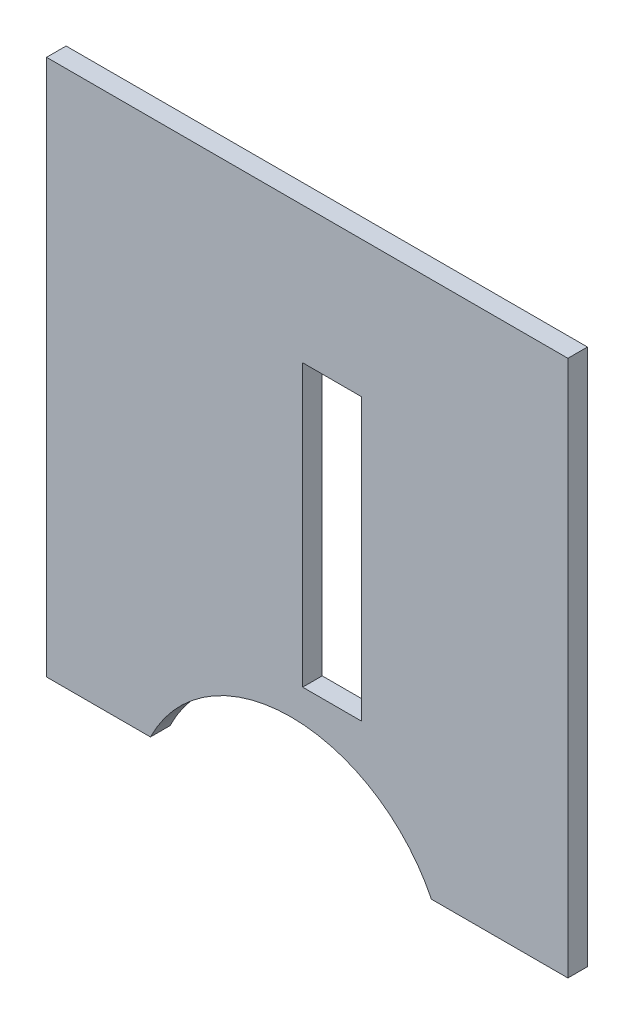
SolidWorks part; units mm, degrees
ref_plane "Front Plane" through (0, 0, 0) normal (0, 0, 1) x (1, 0, 0)
ref_plane "Top Plane" through (0, 0, 0) normal (0, 1, 0) x (1, 0, 0)
ref_plane "Right Plane" through (0, 0, 0) normal (1, 0, 0) x (0, 0, -1)
sketch "Sketch1" plane through (0, 0, 0) normal (0, 0, 1) x (1, 0, 0)
  line L0 (0, -82.357) -> (15.9432, -82.357)
  line L1 (0, 0) -> (80, 0)
  line L2 (0, 0) -> (0, -82.357)
  line L3 (0, -82.357) -> (80, -82.357) construction
  line L4 (80, 0) -> (80, -82.357)
  line L5 (39.3, -20.9432) -> (48.3, -20.9432)
  line L6 (39.3, -20.9432) -> (39.3, -64.0568)
  line L7 (39.3, -64.0568) -> (48.3, -64.0568)
  line L8 (48.3, -20.9432) -> (48.3, -64.0568)
  line L9 (59.0568, -82.357) -> (80, -82.357)
  circle A0 centre (37.5, -92.907) radius 21 construction
  arc A1 (59.0568, -82.357) -> (15.9432, -82.357) centre (37.5, -92.907) ccw
  circle A2 centre (37.5, -92.907) radius 21 construction
  dimension "D1" = 3
sketch "Sketch2" plane through (0, 0, 0) normal (0, 1, 0) x (1, 0, 0)
  line L1 (80, 0) -> (0, 0)
  line L2 (80, 0) -> (80, 3)
  line L3 (80, 3) -> (0, 3)
  line L4 (0, 0) -> (0, 3)
extrude "Boss-Extrude1" add sketch "Sketch1" against normal up to vertex (3 mm away) up to point (0, 0, -3)
